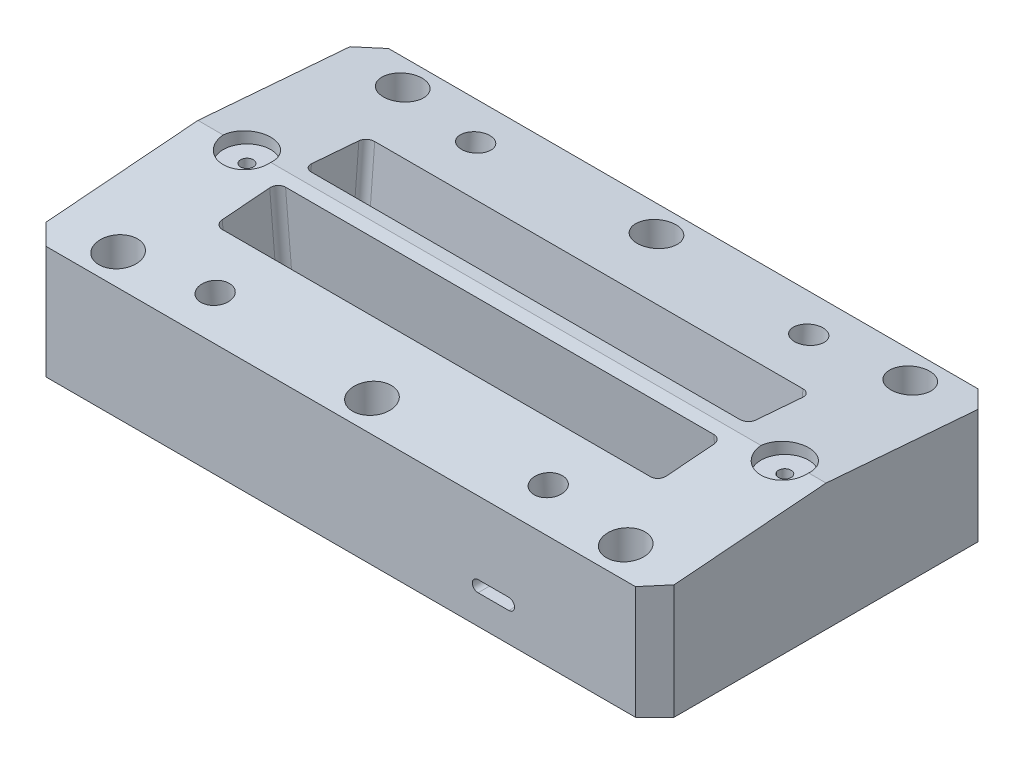
SolidWorks part; units mm, degrees
material "Custom Plastic"
ref_plane "Front Plane" through (0, 0, 0) normal (0, 0, 1) x (1, 0, 0)
ref_plane "Top Plane" through (0, 0, 0) normal (0, 1, 0) x (1, 0, 0)
ref_plane "Right Plane" through (0, 0, 0) normal (1, 0, 0) x (0, 0, -1)
sketch "Sketch1" plane through (0, 0, 0) normal (0, 1, 0) x (1, 0, 0)
  line L1 (0, 0) -> (198, 0)
  line L2 (0, 0) -> (0, 108)
  line L3 (0, 108) -> (198, 108)
  line L4 (198, 0) -> (198, 108)
  dimension "D1" = 198
  dimension "D2" = 108
extrude "Boss-Extrude1" add sketch "Sketch1" along normal blind 40
ref_plane "Left" through (198, 0, 0) normal (1, 0, 0) x (0, 0, -1)
ref_plane "Bot" through (0, 40, 0) normal (0, 1, 0) x (1, 0, 0)
ref_plane "der loco" through (0, 0, -52) normal (0, 0, -1) x (-1, 0, 0)
sketch "Sketch4" plane through (0, 0, 0) normal (0, 1, 0) x (1, 0, 0)
  line L0 (0, 108) -> (0, 0) construction
  line L1 (8.5, 31.5) -> (189.5, 31.5)
  line L2 (8.5, 31.5) -> (8.5, 76.5)
  line L3 (8.5, 76.5) -> (189.5, 76.5)
  line L4 (189.5, 31.5) -> (189.5, 76.5)
  line L5 (0, 0) -> (198, 0) construction
  dimension "D1" = 181
  dimension "D2" = 8.5
  dimension "D3" = 45
  dimension "D4" = 31.5
extrude "Cut-Extrude2" cut sketch "Sketch4" along normal blind 10 contours L2 L1 L4 L3
ref_plane "Plane32" through (0, 10, 0) normal (0, -1, 0) x (-1, 0, 0)
sketch "Sketch5" plane through (198, 0, 0) normal (1, 0, 0) x (0, 0, -1)
  line L0 (54, 40) -> (108, 35.6742)
  line L1 (0, 40) -> (108, 40) construction
  line L2 (108, 35.6742) -> (108, 40)
  line L3 (108, 40) -> (54, 40)
  line L4 (108, 40) -> (108, 0) construction
  dimension "D1" = 4.58
  dimension "D2" = 54
extrude "Cut-Extrude3" cut sketch "Sketch5" against normal up to vertex (198 mm away) up to point (0, 40, 0)
ref_plane "Plane24" through (0, 10, 0) normal (0, -1, 0) x (-1, 0, 0)
sketch "Sketch53" plane through (0, 10, 0) normal (0, -1, 0) x (-1, 0, 0)
  line L0 (-8.5, 51.5) -> (-8.5, 31.5)
  line L1 (-8.5, 76.5) -> (-8.5, 31.5) construction
  line L2 (-8.5, 31.5) -> (-39.5, 31.5)
  line L3 (-8.5, 31.5) -> (-189.5, 31.5) construction
  line L4 (-39.5, 31.5) -> (-8.5, 51.5)
  line L5 (-8.5, 54) -> (-189.5, 54) construction
  line L6 (-189.5, 31.5) -> (-189.5, 76.5) construction
  line L7 (-8.5, 56.5) -> (-8.5, 76.5)
  line L8 (-8.5, 76.5) -> (-39.5, 76.5)
  line L9 (-39.5, 76.5) -> (-8.5, 56.5)
  line L10 (-99, 76.5) -> (-99, 31.5) construction
  line L11 (-8.5, 76.5) -> (-189.5, 76.5) construction
  line L12 (-8.5, 31.5) -> (-189.5, 31.5) construction
  line L13 (-158.5, 76.5) -> (-189.5, 56.5)
  line L14 (-189.5, 76.5) -> (-158.5, 76.5)
  line L15 (-189.5, 56.5) -> (-189.5, 76.5)
  line L16 (-158.5, 31.5) -> (-189.5, 51.5)
  line L17 (-189.5, 31.5) -> (-158.5, 31.5)
  line L18 (-189.5, 51.5) -> (-189.5, 31.5)
  dimension "D1" = 31
  dimension "D2" = 20
extrude "Boss-Extrude11" add sketch "Sketch53" along normal up to surface (10 mm away) up to face at (99, 0, -54)
ref_plane "izq loco" through (0, 0, -57) normal (0, 0, -1) x (-1, 0, 0)
sketch "Sketch18" plane through (198, 0, 0) normal (1, 0, 0) x (0, 0, -1)
  line L0 (0, 35.6742) -> (0, 40)
  line L1 (0, 40) -> (0, 0) construction
  line L2 (0, 40) -> (54, 40)
  line L3 (54, 40) -> (0, 35.6742)
  line L4 (0, 40) -> (54, 40) construction
  dimension "D1" = 54
  dimension "D2" = 4.58
extrude "Cut-Extrude12" cut sketch "Sketch18" against normal up to surface (198 mm away) up to face at (0, 23.1348, -54)
sketch "Sketch60" plane through (0, 0, 0) normal (0, 1, 0) x (1, 0, 0)
  point P0 (8.5, 31.5)
  point P1 (39.5, 31.5)
  point P2 (8.5, 76.5)
  point P6 (39.5, 76.5)
  dimension "D1" = 20
  dimension "D2" = 31
  dimension "D3" = 20
  dimension "D4" = 31
ref_axis "Axis6" through (8.5, 0, -31.5) along (1, 0, 0)
sketch "Sketch69" plane through (0, 10, 0) normal (0, -1, 0) x (-1, 0, 0)
  point P0 (-39.5, 56.5)
  point P1 (-8.5, 51.5)
  point P2 (-38.5, 51.5)
  point P3 (-8.5, 56.5)
  dimension "D1" = 31
  dimension "D2" = 20
  dimension "D3" = 20
  dimension "D4" = 30
sketch "der loco axis" plane through (0, 0, -52) normal (0, 0, -1) x (-1, 0, 0)
  point P0 (-8.5, 8.5)
  point P1 (-38.5, 8.5)
  dimension "D1" = 1.5
sketch "izq loco axis" plane through (0, 0, -57) normal (0, 0, -1) x (-1, 0, 0)
  line L0 (-39.5, 0) -> (-39.5, 10) construction
  line L1 (-8.5, 0) -> (-8.5, 10) construction
  point P0 (-8.5, 8.4959)
  point P1 (-39.5, 8.4959)
  dimension "D1" = 1.5041
ref_plane "Plane3" through (0, 44.0431, -3.5282) normal (0, 0.9968, -0.0799) x (1, 0, 0)
ref_axis "Axis8" through (39.5, 0, -76.5) along (-1, 0, 0)
ref_axis "Axis9" through (8.5, 8.4959, -57) along (1, 0, 0)
ref_axis "Axis10" through (38.5, 8.5, -52) along (-1, 0, 0)
ref_plane "Izq bueno" through (0, 28.0127, -12.2048) normal (0, 0.9168, -0.3994) x (1, 0, 0)
sketch "Izq" plane through (0, 28.0127, -12.2048) normal (0, 0.9168, -0.3994) x (1, 0, 0)
  line L0 (8.5, 48.8622) -> (29.5, 70.1326)
  line L1 (29.5, 70.1326) -> (8.5, 70.1326)
  line L2 (8.5, 70.1326) -> (8.5, 48.8622)
  dimension "D1" = 21
extrude "Cut-Extrude28" cut sketch "Izq" against normal blind 14.5
ref_plane "Der bueno" through (0, -11.1449, -4.6211) normal (0, 0.9237, 0.383) x (1, 0, 0)
sketch "Der" plane through (0, -11.1449, -4.6211) normal (0, 0.9237, 0.383) x (1, 0, 0)
  line L0 (8.5, 51.2902) -> (29.5, 29.0979)
  line L1 (29.5, 29.0979) -> (8.5, 29.0979)
  line L2 (8.5, 29.0979) -> (8.5, 51.2902)
  dimension "D1" = 21
extrude "Cut-Extrude29" cut sketch "Der" against normal blind 14.5
sketch "Sketch97" plane through (0, 0, 0) normal (0, 1, 0) x (1, 0, 0)
  line L0 (8.5, 57.5) -> (29.5, 76.5)
  line L1 (29.5, 76.5) -> (158.5, 76.5)
  line L3 (158.5, 31.5) -> (29.5, 31.5)
  line L4 (29.5, 31.5) -> (8.5, 51.5)
  line L5 (8.5, 51.5) -> (8.5, 57.5)
  line L7 (158.5, 76.5) -> (189.5, 56.5)
  line L8 (189.5, 56.5) -> (189.5, 51.5)
  line L9 (189.5, 51.5) -> (158.5, 31.5)
  line L10 (39.5, 76.5) -> (158.5, 76.5) construction
  dimension "D1" = 6
extrude "Cut-Extrude40" cut sketch "Sketch97" along normal up to surface (10 mm away) up to face at (99, 10, -54)
ref_axis "Axis11" through (99, 0, -108) along (0, 0, 1)
ref_plane "Plane33" through (99, 0, 0) normal (1, 0, 0) x (0, 0, -1)
mirror "Mirror2" about plane through (99, 0, 0) normal (1, 0, 0) of "Cut-Extrude29", "Cut-Extrude40", "Cut-Extrude28"
sketch "Sketch6" plane through (0, 44.0431, -3.5282) normal (0, 0.9968, -0.0799) x (1, 0, 0)
  line L0 (0, 50.6335) -> (198, 50.6335) construction
  line L1 (28.9, 78.0335) -> (169.5, 78.0335)
  line L2 (25.9, 75.0335) -> (25.9, 54.4335)
  line L3 (28.9, 51.4335) -> (169.5, 51.4335)
  line L4 (172.5, 75.0335) -> (172.5, 54.4335)
  line L7 (28.6, 54.1335) -> (169.8, 54.1335)
  line L8 (28.6, 54.1335) -> (28.6, 75.3335)
  line L9 (28.6, 75.3335) -> (169.8, 75.3335)
  line L10 (169.8, 54.1335) -> (169.8, 75.3335)
  line L13 (198, 50.6335) -> (198, 104.8065) construction
  arc A0 (169.5, 78.0335) -> (172.5, 75.0335) centre (169.5, 75.0335) cw
  arc A1 (169.5, 51.4335) -> (172.5, 54.4335) centre (169.5, 54.4335) ccw
  arc A2 (25.9, 54.4335) -> (28.9, 51.4335) centre (28.9, 54.4335) ccw
  arc A3 (28.9, 78.0335) -> (25.9, 75.0335) centre (28.9, 75.0335) ccw
  dimension "D1" = 3
  dimension "D2" = 146.6
  dimension "D3" = 20.6
  dimension "D4" = 25.5
  dimension "D5" = 3.5
  dimension "D6" = 2.7
  dimension "D7" = 2.7
  dimension "D8" = 2.7
  dimension "D9" = 2.7
sketch "Sketch9" plane through (0, 40, 0) normal (0, 1, 0) x (1, 0, 0)
  line L1 (0, 54) -> (198, 54) construction
  circle A0 centre (15.45, 54) radius 8
  dimension "D1" = 16
  dimension "D2" = 15.45
sketch "Sketch12" plane through (0, 40, 0) normal (0, 1, 0) x (1, 0, 0)
  line L1 (0, 108) -> (198, 108) construction
  line L4 (0, 0) -> (198, 0) construction
  circle A0 centre (19.7, 98.85) radius 3.15
  circle A1 centre (99.7, 9.15) radius 3.15
  circle A2 centre (179.7, 9.15) radius 3.15
  circle A3 centre (19.7, 9.15) radius 3.15
  circle A4 centre (99.7, 98.85) radius 3.15
  circle A5 centre (179.7, 98.85) radius 3.15
  dimension "D1" = 9.15
  dimension "D2" = 6.3
  dimension "D3" = 9.15
  dimension "D4" = 19.7
  dimension "D7" = 80
  dimension "D9" = 80
extrude "Cut-Extrude9" cut sketch "Sketch12" against normal through all
sketch "Sketch13" plane through (0, 44.0431, -3.5282) normal (0, 0.9968, -0.0799) x (1, 0, 0)
  line L1 (0, 104.8065) -> (198, 104.8065) construction
  line L2 (198, 50.6335) -> (198, 104.8065) construction
  line L3 (0, 50.6335) -> (0, 104.8065) construction
  circle A0 centre (46.5, 91.8065) radius 4.5
  circle A1 centre (151.5, 91.8065) radius 4.5
  dimension "D1" = 9
  dimension "D4" = 9
  dimension "D2" = 46.5
  dimension "D3" = 13
  dimension "D5" = 46.5
extrude "Cut-Extrude10" cut sketch "Sketch13" against normal blind 16.5
sketch "Sketch14" plane through (0, 35.2123, 5.7666) normal (0, 0.9968, 0.0799) x (1, 0, 0)
  line L3 (198, 5.7851) -> (198, 59.9581) construction
  line L4 (0, 59.9581) -> (198, 59.9581) construction
  circle A0 centre (46.5, 18.7396) radius 4.5
  circle A1 centre (151.5, 18.7396) radius 4.5
  dimension "D1" = 9
  dimension "D2" = 9
  dimension "D3" = 46.5
  dimension "D4" = 41.2185
  dimension "D5" = 46.5
extrude "Cut-Extrude11" cut sketch "Sketch14" against normal blind 16.5
ref_plane "Plane9" through (0, 35.4468, 2.8395) normal (0, 0.9968, 0.0799) x (1, 0, 0)
sketch "Sketch23" plane through (0, 35.4468, 2.8395) normal (0, 0.9968, 0.0799) x (1, 0, 0)
  line L0 (0, 57.0216) -> (198, 57.0216) construction
  line L1 (28.9, 56.2216) -> (169.5, 56.2216)
  line L2 (25.9, 53.2216) -> (25.9, 32.6216)
  line L3 (28.9, 29.6216) -> (169.5, 29.6216)
  line L4 (172.5, 53.2216) -> (172.5, 32.6216)
  line L7 (28.6, 53.5216) -> (169.8, 53.5216)
  line L8 (28.6, 53.5216) -> (28.6, 32.3216)
  line L9 (28.6, 32.3216) -> (169.8, 32.3216)
  line L10 (169.8, 53.5216) -> (169.8, 32.3216)
  line L12 (198, 2.8486) -> (198, 57.0216) construction
  arc A0 (169.5, 56.2216) -> (172.5, 53.2216) centre (169.5, 53.2216) cw
  arc A1 (169.5, 29.6216) -> (172.5, 32.6216) centre (169.5, 32.6216) ccw
  arc A2 (25.9, 32.6216) -> (28.9, 29.6216) centre (28.9, 32.6216) ccw
  arc A3 (28.9, 56.2216) -> (25.9, 53.2216) centre (28.9, 53.2216) ccw
  point P10 (172.5, 56.2216)
  point P15 (25.9, 29.6216)
  point P18 (25.9, 56.2216)
  dimension "D5" = 3
  dimension "D1" = 146.6
  dimension "D2" = 20.6
  dimension "D3" = 3.5
  dimension "D4" = 25.5
  dimension "D6" = 2.7
  dimension "D7" = 2.7
  dimension "D8" = 2.7
  dimension "D9" = 2.7
sketch "Sketch41" plane through (0, 0, 0) normal (0, 1, 0) x (1, 0, 0)
  line L0 (198, 0) -> (198, 108) construction
  line L1 (198, 108) -> (0, 108) construction
  line L2 (0, 0) -> (198, 0) construction
  circle A0 centre (139.5, 9) radius 2.9
  circle A1 centre (139.5, 99) radius 2.9
  dimension "D1" = 5.8
  dimension "D4" = 5.8
  dimension "D2" = 58.5
  dimension "D3" = 58.5
  dimension "D5" = 9
  dimension "D6" = 9
extrude "Cut-Extrude21" cut sketch "Sketch41" along normal blind 7
sketch "Sketch42" plane through (0, 0, 0) normal (0, 0, 1) x (1, 0, 0)
  line L0 (198, 35.6742) -> (198, 0) construction
  line L5 (0, 0) -> (198, 0) construction
  line L6 (142.3, 12.8) -> (152, 12.8)
  line L7 (142.3, 9.2) -> (152, 9.2)
  arc A0 (142.3, 12.8) -> (142.3, 9.2) centre (142.3, 11) ccw
  arc A2 (152, 12.8) -> (152, 9.2) centre (152, 11) cw
  dimension "D2" = 1.8
  dimension "D3" = 1.8
  dimension "D1" = 9.7
  dimension "D5" = 46
  dimension "D6" = 11
extrude "Cut-Extrude22" cut sketch "Sketch42" against normal blind 10
ref_plane "Plane19" through (0, 0, -108) normal (0, 0, -1) x (-1, 0, 0)
sketch "Sketch43" plane through (0, 0, -108) normal (0, 0, -1) x (-1, 0, 0)
  line L0 (-55.7, 11) -> (-46, 11) construction
  line L1 (-55.7, 12.8) -> (-46, 12.8)
  line L2 (-55.7, 9.2) -> (-46, 9.2)
  line L3 (-198, 0) -> (0, 0) construction
  line L4 (0, 35.6742) -> (0, 0) construction
  arc A0 (-55.7, 12.8) -> (-55.7, 9.2) centre (-55.7, 11) ccw
  arc A1 (-46, 9.2) -> (-46, 12.8) centre (-46, 11) ccw
  point P2 (-50.85, 11)
  dimension "D2" = 1.8
  dimension "D1" = 9.7
  dimension "D3" = 11
  dimension "D4" = 46
extrude "Cut-Extrude23" cut sketch "Sketch43" against normal blind 10
sketch "Sketch84" plane through (0, 44.0431, -3.5282) normal (0, 0.9968, -0.0799) x (1, 0, 0)
  line L0 (0, 50.6335) -> (198, 50.6335) construction
  line L1 (31.7, 54.7335) -> (166.7, 54.7335)
  line L2 (29.2, 57.2335) -> (29.2, 72.2335)
  line L3 (31.7, 74.7335) -> (166.7, 74.7335)
  line L4 (169.2, 57.2335) -> (169.2, 72.2335)
  line L7 (0, 50.6335) -> (0, 104.8065) construction
  arc A0 (166.7, 54.7335) -> (169.2, 57.2335) centre (166.7, 57.2335) ccw
  arc A1 (166.7, 74.7335) -> (169.2, 72.2335) centre (166.7, 72.2335) cw
  arc A2 (29.2, 72.2335) -> (31.7, 74.7335) centre (31.7, 72.2335) cw
  arc A3 (31.7, 54.7335) -> (29.2, 57.2335) centre (31.7, 57.2335) cw
  point P10 (169.2, 54.7335)
  point P13 (169.2, 74.7335)
  point P16 (29.2, 74.7335)
  point P19 (169.2, 64.7335)
  dimension "D5" = 2.5
  dimension "D1" = 140
  dimension "D2" = 20
  dimension "D3" = 4.1
  dimension "D4" = 29.2
extrude "Cut-Extrude35" cut sketch "Sketch84" against normal blind 55.4
sketch "Sketch83" plane through (0, 35.4468, 2.8395) normal (0, 0.9968, 0.0799) x (1, 0, 0)
  line L1 (31.7, 52.9216) -> (166.7, 52.9216)
  line L2 (29.2, 50.4216) -> (29.2, 35.4216)
  line L3 (31.7, 32.9216) -> (166.7, 32.9216)
  line L4 (169.2, 50.4216) -> (169.2, 35.4216)
  line L7 (0, 57.0216) -> (198, 57.0216) construction
  line L8 (0, 57.0216) -> (0, 2.8486) construction
  arc A0 (166.7, 32.9216) -> (169.2, 35.4216) centre (166.7, 35.4216) ccw
  arc A1 (166.7, 52.9216) -> (169.2, 50.4216) centre (166.7, 50.4216) cw
  arc A2 (29.2, 35.4216) -> (31.7, 32.9216) centre (31.7, 35.4216) ccw
  arc A3 (31.7, 52.9216) -> (29.2, 50.4216) centre (31.7, 50.4216) ccw
  point P12 (169.2, 52.9216)
  point P15 (29.2, 32.9216)
  point P18 (29.2, 52.9216)
  point P19 (169.2, 42.9216)
  dimension "D5" = 2.5
  dimension "D1" = 140
  dimension "D2" = 20
  dimension "D3" = 29.2
  dimension "D4" = 4.1
extrude "Cut-Extrude34" cut sketch "Sketch83" against normal blind 55.4
sketch "Sketch85" plane through (0, 40, 0) normal (0, 1, 0) x (1, 0, 0)
  line L0 (0, 101.9) -> (6.1, 108)
  line L3 (6.1, 108) -> (0, 108)
  line L4 (0, 108) -> (0, 101.9)
  line L5 (0, 0) -> (6.1, 0)
  line L7 (6.1, 0) -> (0, 6.1)
  line L9 (0, 6.1) -> (0, 0)
  line L10 (198, 6.1) -> (191.9, 0)
  line L11 (198, 0) -> (198, 54) construction
  line L12 (0, 0) -> (198, 0) construction
  line L13 (191.9, 0) -> (198, 0)
  line L14 (198, 0) -> (198, 6.1)
  line L15 (198, 108) -> (191.9, 108)
  line L16 (0, 108) -> (198, 108) construction
  line L17 (191.9, 108) -> (198, 101.9)
  line L18 (198, 54) -> (198, 108) construction
  line L19 (198, 101.9) -> (198, 108)
  line L20 (0, 54) -> (0, 108) construction
  line L21 (0, 108) -> (198, 108) construction
  line L22 (0, 0) -> (198, 0) construction
  line L23 (0, 54) -> (0, 0) construction
  dimension "D1" = 6.1
  dimension "D2" = 6.1
  dimension "D3" = 6.1
  dimension "D4" = 6.1
  dimension "D5" = 6.1
  dimension "D6" = 6.1
  dimension "D7" = 6.1
extrude "Cut-Extrude36" cut sketch "Sketch85" against normal blind 55.4
sketch "Sketch90" plane through (0, 40, 0) normal (0, 1, 0) x (1, 0, 0)
  circle A0 centre (19.7, 9.15) radius 6.1
  circle A1 centre (99.7, 9.15) radius 6.1
  circle A2 centre (179.7, 9.15) radius 6.1
  circle A3 centre (99.7, 98.85) radius 6.1
  circle A4 centre (179.7, 98.85) radius 6.1
  circle A5 centre (19.7, 98.85) radius 6.1
  circle A6 centre (179.7, 98.85) radius 3.15 construction
  circle A7 centre (99.7, 98.85) radius 3.15 construction
  dimension "D1" = 12.2
  dimension "D2" = 3
  dimension "D3" = 2
extrude "Cut-Extrude38" cut sketch "Sketch90" against normal blind 17
sketch "Sketch96" plane through (0, 0, 0) normal (0, 1, 0) x (1, 0, 0)
  line L0 (0, 54) -> (198, 54) construction
  line L1 (198, 6.1) -> (198, 101.9) construction
  circle A0 centre (15.45, 54) radius 2
  circle A1 centre (185, 54) radius 2
  dimension "D1" = 4
  dimension "D2" = 4
  dimension "D3" = 13
extrude "Cut-Extrude39" cut sketch "Sketch96" along normal through all
sketch "Sketch98" plane through (0, 40, 0) normal (0, 1, 0) x (1, 0, 0)
  circle A0 centre (185, 54) radius 7.5
  circle A1 centre (15.45, 54) radius 7.5
  dimension "D1" = 15
  dimension "D2" = 15
extrude "Cut-Extrude41" cut sketch "Sketch98" against normal blind 4
sketch "Sketch99" plane through (198, 0, 0) normal (1, 0, 0) x (0, 0, -1)
  line L0 (57.4888, 39.7205) -> (78.6211, 38.0277) construction
  line L1 (54, -136.5975) -> (68.055, 38.8741) construction
  line L2 (54, -136.5975) -> (175.8472, -146.3583) construction
  line L3 (54, 40) -> (101.9, 36.1629) construction
  line L4 (54, -136.5975) -> (-67.8472, -146.3583) construction
  line L5 (6.1, 36.1629) -> (54, 40) construction
  line L6 (54.0015, -136.5975) -> (39.945, 38.8741) construction
  line L7 (-68.2375, -136.5975) -> (176.2375, -136.5975) construction
  line L8 (54, -136.5975) -> (39.945, 38.8741) construction
  line L9 (32.469, 38.2752) -> (47.4211, 39.473) construction
  line L10 (53.9985, -136.5975) -> (68.055, 38.8741) construction
  circle A0 centre (54, -136.5975) radius 122.2375
  point P17 (0, 0)
  point P19 (39.945, 38.8741)
  dimension "D1" = 244.475
  dimension "D2" = 136.5975
  dimension "D3" = 90
  dimension "D4" = 90
